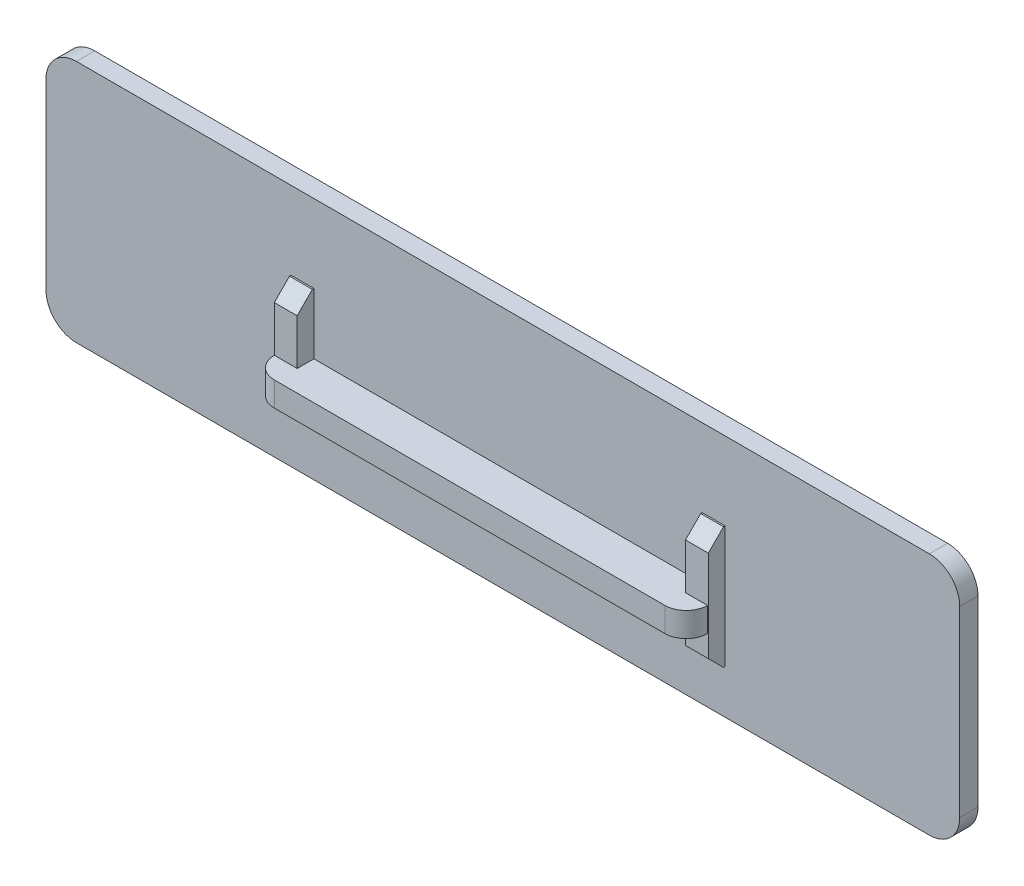
SolidWorks part; units mm, degrees
ref_plane "前视基准面" through (0, 0, 0) normal (0, 0, 1) x (1, 0, 0)
ref_plane "上视基准面" through (0, 0, 0) normal (0, 1, 0) x (1, 0, 0)
ref_plane "右视基准面" through (0, 0, 0) normal (1, 0, 0) x (0, 0, -1)
sketch "草图1" plane through (0, 0, 0) normal (0, 0, 1) x (1, 0, 0)
  line L1 (-30, 8) -> (30, 8)
  line L2 (-30, 8) -> (-30, -8)
  line L3 (-30, -8) -> (30, -8)
  line L4 (30, 8) -> (30, -8)
  line L5 (-30, 8) -> (30, -8) construction
  line L6 (-30, -8) -> (30, 8) construction
  point P0 (0, 0)
  dimension "D1" = 60
  dimension "D2" = 16
extrude "凸台-拉伸1" add sketch "草图1" along normal blind 1.2
sketch "草图3" plane through (0, 0, 1.2) normal (0, 0, 1) x (1, 0, 0)
  line L1 (-13.9089, 2.8832) -> (-12.4089, 2.8832)
  line L2 (-13.9089, 2.8832) -> (-13.9089, -5.1168)
  line L3 (-13.9089, -5.1168) -> (-12.4089, -5.1168)
  line L4 (-12.4089, 2.8832) -> (-12.4089, -5.1168)
  line L5 (13.0911, -5.1168) -> (14.5911, -5.1168)
  line L6 (13.0911, -5.1168) -> (13.0911, 2.8832)
  line L7 (13.0911, 2.8832) -> (14.5911, 2.8832)
  line L8 (14.5911, -5.1168) -> (14.5911, 2.8832)
extrude "凸台-拉伸3" add sketch "草图3" along normal blind 1.1
chamfer "倒角3" distance 1 angle 45 4 edges at (13.8411, -5.1168, 2.3) (-13.1589, -5.1168, 2.3) (13.8411, 2.8832, 2.3) (-13.1589, 2.8832, 2.3)
sketch "草图4" plane through (0, 0, 1.2) normal (0, 0, 1) x (1, 0, 0)
  line L0 (-13.9089, 1.8832) -> (-13.9089, -4.1168) construction
  line L1 (-13.9089, -1.1168) -> (14.5366, -1.1168)
  line L2 (-13.9089, -1.1168) -> (-13.9089, -2.7168)
  line L3 (-13.9089, -2.7168) -> (14.5366, -2.7168)
  line L4 (14.5366, -1.1168) -> (14.5366, -2.7168)
  dimension "D1" = 1.6
extrude "凸台-拉伸4" add sketch "草图4" along normal blind 2.5
fillet "圆角3" radius 1.4 2 edges at (14.5366, -1.9168, 3.7) (-13.9089, -1.9168, 3.7)
fillet "圆角4" radius 2 4 edges at (30, -8, 0.6) (30, 8, 0.6) (-30, -8, 0.6) (-30, 8, 0.6)
